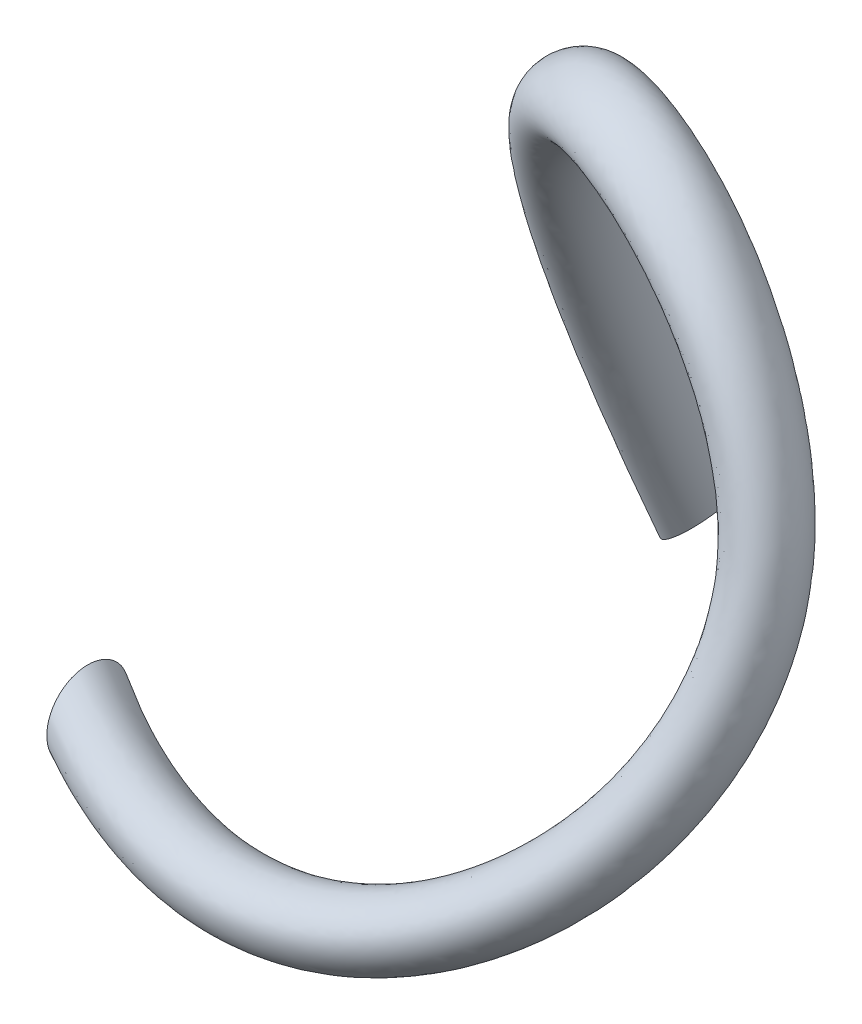
SolidWorks part; units mm, degrees
note: '?' marks a value the reader was unsure of.
material "PUR"
ref_plane "Front Plane" through (0, 0, 0) normal (0, 0, 1) x (1, 0, 0)
ref_plane "Top Plane" through (0, 0, 0) normal (0, 1, 0) x (1, 0, 0)
ref_plane "Right Plane" through (0, 0, 0) normal (1, 0, 0) x (0, 0, -1)
sketch3d "3DSketch1"
  line L0 (7.2177, 3.1324, -22.1456) -> (7.2177, 9.1786, -19.6476) construction
  line L1 (7.2177, 2.2181, -22.5234) -> (7.2177, 4.4713, -21.5925) construction
  line L2 (7.2177, 4.2236, -21.6948) -> (7.2177, 5.1478, -21.313) construction
  spline S0 degree 3 poles (0, 0, 0) (13.1876, -8.3166, 4.6029) (42.4144, 16.6632, -13.3456) (5.3545, 39.897, -7.1543) (7.2177, 0.8804, -23.0761) knots 0 0 0 0 0.494445 1 1 1 1
  point P0 (0, 0, 0)
  point P1 (25.8842, 15.9588, -7.2446)
  point P3 (7.2177, 0.8804, -23.0761)
  point P7 (7.2177, 10.763, -18.993)
  point P8 (19.2, 0.8707, -1.0526)
  point P22 (23.3318, 22.4442, -8.4709)
sketch "Sketch1" plane through (0, 0, 0) normal (1, 0, 0) x (0, 0, -1)
  circle A0 centre (0, 0) radius 2
  circle A1 centre (0, 0) radius 1
  dimension "D1" = 2
  dimension "D2" = 4
sweep "Sweep1" add profiles "Sketch1" path "3DSketch1"
ref_axis "Axis1" through (16.6702, 0, 0) along (-1, 0, 0)?
